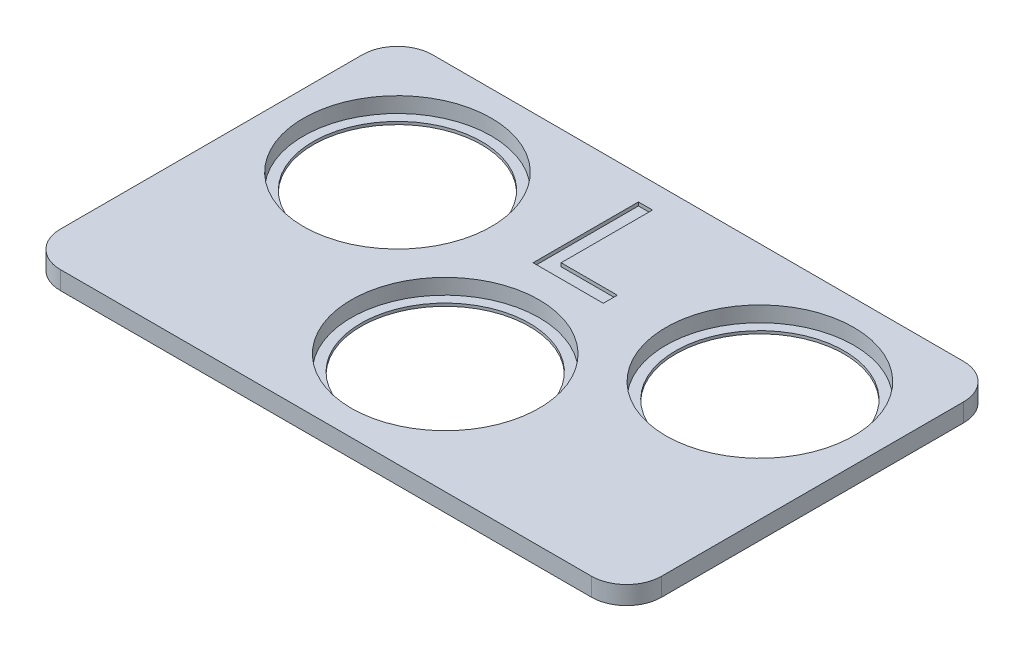
SolidWorks part; units mm, degrees
ref_plane "Front Plane" through (0, 0, 0) normal (0, 0, 1) x (1, 0, 0)
ref_plane "Top Plane" through (0, 0, 0) normal (0, 1, 0) x (1, 0, 0)
ref_plane "Right Plane" through (0, 0, 0) normal (1, 0, 0) x (0, 0, -1)
sketch "Sketch1" plane through (0, 0, 0) normal (0, 1, 0) x (1, 0, 0)
  line L1 (-42.8, 26.49) -> (42.8, 26.49)
  line L2 (-42.8, 26.49) -> (-42.8, -26.49)
  line L3 (-42.8, -26.49) -> (42.8, -26.49)
  line L4 (42.8, 26.49) -> (42.8, -26.49)
  line L5 (-42.8, 26.49) -> (42.8, -26.49) construction
  line L6 (-42.8, -26.49) -> (42.8, 26.49) construction
  point P0 (0, 0)
  dimension "D1" = 85.6
  dimension "D2" = 52.98
extrude "Boss-Extrude1" add sketch "Sketch1" along normal blind 2.6
sketch "Sketch2" plane through (0, 2.6, 0) normal (0, 1, 0) x (1, 0, 0)
  line L0 (-42.8, 26.49) -> (-42.8, -26.49) construction
  line L1 (42.8, 26.49) -> (-42.8, 26.49) construction
  line L2 (42.8, -26.49) -> (42.8, 26.49) construction
  circle A0 centre (-25.8, 9.49) radius 13.375
  circle A1 centre (0, -9.51) radius 13.375
  circle A2 centre (25.8, 9.49) radius 13.375
  point P2 (-29.7447, 11.3188)
  point P3 (-28.4286, 9.3007)
  point P4 (-26.937, 10.6169)
  point P9 (0, -11.1433)
  point P10 (25.7086, 10.6169)
  dimension "D1" = 26.75
  dimension "D2" = 26.75
  dimension "D3" = 26.75
  dimension "D4" = 17
  dimension "D5" = 17
  dimension "D6" = 17
  dimension "D7" = 19
extrude "Cut-Extrude1" cut sketch "Sketch2" against normal blind 2.2
sketch "Sketch3" plane through (0, 0.4, 0) normal (0, 1, 0) x (1, 0, 0)
  circle A0 centre (-25.8, 9.49) radius 12
  circle A1 centre (0, -9.51) radius 12
  circle A2 centre (25.8, 9.49) radius 12
  dimension "D1" = 24
  dimension "D2" = 24
  dimension "D3" = 24
extrude "Cut-Extrude2" cut sketch "Sketch3" against normal blind 1.75
fillet "Fillet1" radius 5 4 edges at (42.8, 1.3, -26.49) (42.8, 1.3, 26.49) (-42.8, 1.3, 26.49) (-42.8, 1.3, -26.49)
sketch "Sketch4" plane through (0, 2.6, 0) normal (0, 1, 0) x (1, 0, 0)
  line L0 (-3, 10) -> (5, 10)
  line L1 (-5, 23) -> (-3, 23)
  line L2 (-5, 23) -> (-5, 8)
  line L3 (-5, 8) -> (-3, 8)
  line L4 (-3, 23) -> (-3, 10)
  line L5 (-5, 23) -> (-3, 8) construction
  line L6 (-5, 8) -> (-3, 23) construction
  line L7 (-5, 8) -> (5, 8)
  line L8 (-5, 8) -> (-5, 10)
  line L9 (-5, 10) -> (-4.7333, 10)
  line L10 (5, 8) -> (5, 10)
  point P0 (-4, 15.5)
  point P8 (-6.9693, 5.2311)
  point P9 (0, 8)
  dimension "D1" = 2
  dimension "D2" = 2
  dimension "D3" = 10
  dimension "D4" = 15
  dimension "D5" = 8
  dimension "D6" = 2
extrude "Cut-Extrude3" cut sketch "Sketch4" against normal blind 0.5 contours L7 L10 L0 L4 L1 L2 L3 region at (1, 2.6, -9.8197)
equation "\"D6@Sketch2\"=\"D4@Sketch2\""
equation "\"D2@Sketch2\"=\"D1@Sketch2\""
equation "\"D3@Sketch2\"=\"D1@Sketch2\""
